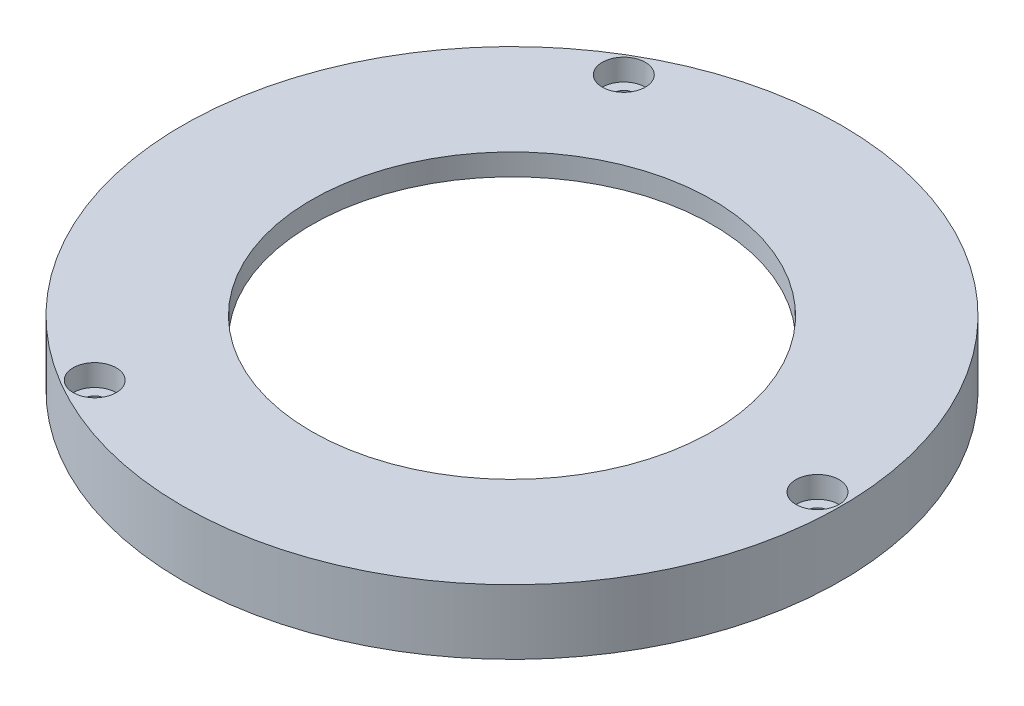
SolidWorks part; units mm, degrees
ref_plane "Front Plane" through (0, 0, 0) normal (0, 0, 1) x (1, 0, 0)
ref_plane "Top Plane" through (0, 0, 0) normal (0, 1, 0) x (1, 0, 0)
ref_plane "Right Plane" through (0, 0, 0) normal (1, 0, 0) x (0, 0, -1)
sketch "Sketch1" plane through (0, 0, 0) normal (0, 1, 0) x (1, 0, 0)
  line L0 (0, 0) -> (42.5, 0) construction
  circle A0 centre (0, 0) radius 45.85
  circle A1 centre (0, 0) radius 27.9
  circle A2 centre (42.5, 0) radius 1.5635
  circle A3 centre (-21.25, -36.8061) radius 1.5635
  circle A4 centre (-21.25, 36.8061) radius 1.5635
  circle A5 centre (0, 0) radius 39.3
  point P13 (0, 0)
  dimension "D1" = 91.7
  dimension "D2" = 55.8
  dimension "D4" = 3.127
  dimension "D6" = 78.6
  dimension "D3" = 42.5
  dimension "D5" = 3
extrude "Boss-Extrude1" add sketch "Sketch1" against normal blind 6 contours A0 A5 A2 A4 A3 region at (-44.5532, 0, 0)
extrude "Boss-Extrude2" add sketch "Sketch1<4>" along normal blind 3 contours A1 A5 | A0 A5 A2 A4 A3 region at (-44.5532, 0, 0) region at (-38.1884, 0, 0)
sketch "Sketch1<4>" plane through (0, 0, 0) normal (0, 1, 0) x (1, 0, 0) same geometry as "Sketch1"
sketch "Sketch2" plane through (0, 3, 0) normal (0, 1, 0) x (1, 0, 0)
  circle A0 centre (42.5, 0) radius 3
  circle A1 centre (-21.25, -36.8061) radius 3
  circle A2 centre (-21.25, 36.8061) radius 3
  point P9 (0, 0)
  dimension "D1" = 6
  dimension "D2" = 3
extrude "Cut-Extrude1" cut sketch "Sketch2" against normal blind 3
equation "\"bearing_21_OD\"= 21mm"
equation "\"pin_cirlce_diameter\"= 75mm"
equation "\"pin_diam\"= 6mm"
equation "\"gear_thickness\"= 4mm"
equation "\"ball_bearing_diam\"= 3.214mm"
equation "\"bearing_21_outer_clearance\"= 0.127mm'change this"
equation "\"bearing_15_OD\"= 15mm"
equation "\"bearing_15_outer_clearance\"= 0mm'change this"
equation "\"thrust_bearing_thickness\"= 5mm'measure this irl and change"
equation "\"D1@Boss-Extrude1\"=\"thrust_bearing_thickness\"+1mm"
